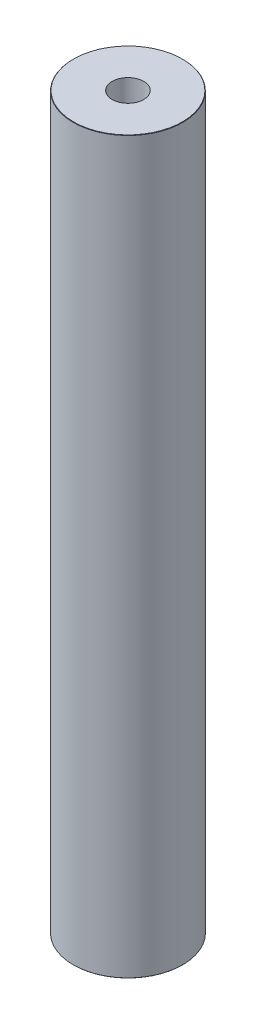
SolidWorks part; units mm, degrees
ref_plane "Front Plane" through (0, 0, 0) normal (0, 0, 1) x (1, 0, 0)
ref_plane "Top Plane" through (0, 0, 0) normal (0, 1, 0) x (1, 0, 0)
ref_plane "Right Plane" through (0, 0, 0) normal (1, 0, 0) x (0, 0, -1)
sketch "Sketch1" plane through (0, 0, 0) normal (0, 1, 0) x (1, 0, 0)
  circle A0 centre (0, 0) radius 45
  dimension "SHAFT_OD" = 90
extrude "Boss-Extrude1" add sketch "Sketch1" along normal blind 600
sketch "Sketch2" plane through (0, 0, 0) normal (0, 1, 0) x (1, 0, 0)
  circle A0 centre (0, 0) radius 12.9663
  dimension "BORE_D" = 25.9325
extrude "Cut-Extrude1" cut sketch "Sketch2" along normal through all
chamfer "Chamfer1" distance 0.2713 angle 45 2 edges at (0, 600, 45) (0, 0, 45)
